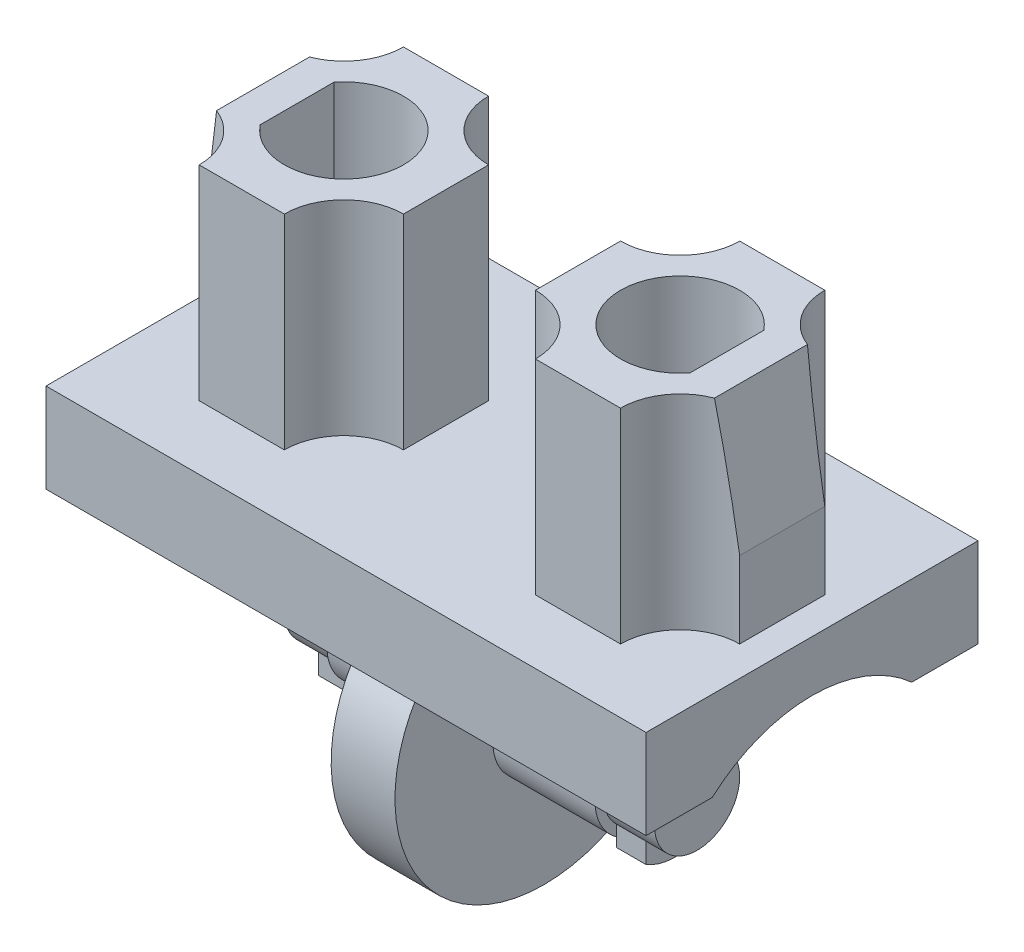
SolidWorks part; units mm, degrees
ref_plane "Front Plane" through (0, 0, 0) normal (0, 0, 1) x (1, 0, 0)
ref_plane "Top Plane" through (0, 0, 0) normal (0, 1, 0) x (1, 0, 0)
ref_plane "Right Plane" through (0, 0, 0) normal (1, 0, 0) x (0, 0, -1)
sketch "Sketch1" plane through (0, 0, 0) normal (1, 0, 0) x (0, 0, -1)
  line L0 (0, 0) -> (0, -4.7) construction
  line L1 (2.3431, -2.1) -> (3.9, -2.1)
  line L2 (-3.9, -2.1) -> (-2.3431, -2.1)
  line L3 (-3.9, -2.1) -> (-3.9, 0)
  line L4 (-3.9, 0) -> (3.9, 0)
  line L5 (3.9, -2.1) -> (3.9, 0)
  line L6 (-3.9, -2.1) -> (3.9, 0) construction
  line L7 (-3.9, 0) -> (3.9, -2.1) construction
  circle A0 centre (0, -4.7) radius 3.5
  point P4 (0, -1.05)
  dimension "D2" = 7
  dimension "D1" = 4.7
  dimension "D3" = 7.8
  dimension "D4" = 2.1
extrude "Hib Base" add sketch "Sketch1" along normal mid plane 14.1 contours A0 L1 L5 L4 L3 L2 region at (0, -0.9029, 0)
extrude "Leg Joint" add sketch "Sketch1<3>" along normal mid plane 1.5 contours A0 region at (0, -4.7, 0)
sketch "Sketch1<3>" plane through (0, 0, 0) normal (1, 0, 0) x (0, 0, -1) same geometry as "Sketch1"
sketch "Sketch2" plane through (0.75, 0, 0) normal (1, 0, 0) x (0, 0, -1)
  circle A0 centre (0, -4.7) radius 1.2
  dimension "D1" = 2.4
extrude "Leg Peg" add sketch "Sketch2" along normal blind 2.4
sketch "Sketch3" plane through (3.15, 0, 0) normal (1, 0, 0) x (0, 0, -1)
  line L0 (-0.6614, -3.95) -> (0.6614, -3.95)
  arc A0 (-0.6614, -3.95) -> (0.6614, -3.95) centre (0, -4.7) ccw
  dimension "D1" = 2
  dimension "D2" = 0.75
extrude "Leg Peg Inner" add sketch "Sketch3" along normal blind 1.2
sketch "Sketch4" plane through (3.15, 0, 0) normal (1, 0, 0) x (0, 0, -1)
  line L2 (-0.7, -5.8893) -> (-0.7, -5.4141)
  line L4 (0.7, -5.8893) -> (0.7, -5.4141)
  arc A0 (-0.6614, -3.95) -> (0.6614, -3.95) centre (0, -4.7) ccw construction
  arc A1 (-0.7, -5.4141) -> (0.7, -5.4141) centre (0, -4.7) ccw
  arc A2 (-0.7, -5.8893) -> (0.7, -5.8893) centre (0, -4.7) ccw
  arc A3 (-0.9128, -3.665) -> (0.9128, -3.665) centre (0, -4.7) ccw construction
  arc A4 (-0.6614, -3.95) -> (0.6614, -3.95) centre (0, -4.7) ccw construction
  point P6 (0, -5.7)
  point P7 (0, 0)
  point P11 (0, -5.7)
  dimension "D2" = 1.4
  dimension "D1" = 0.38
extrude "Leg Lock" add sketch "Sketch4" along normal blind 0.7
sketch "Sketch5" plane through (0, 0, 0) normal (0, 1, 0) x (1, 0, 0)
  line L0 (0, 0) -> (7.05, 0) construction
  line L1 (7.05, -3.9) -> (7.05, 3.9) construction
  line L3 (1.55, -2.4) -> (6.35, -2.4)
  line L4 (1.55, -2.4) -> (1.55, 2.4)
  line L5 (1.55, 2.4) -> (6.35, 2.4)
  line L6 (6.35, -2.4) -> (6.35, 2.4)
  line L7 (1.55, -2.4) -> (6.35, 2.4) construction
  line L8 (1.55, 2.4) -> (6.35, -2.4) construction
  circle A0 centre (1.55, 2.4) radius 1.4
  circle A1 centre (6.35, 2.4) radius 1.4
  circle A2 centre (6.35, -2.4) radius 1.4
  circle A3 centre (1.55, -2.4) radius 1.4
  point P5 (3.95, 0)
  point P11 (0, 0)
  dimension "D4" = 2.8
  dimension "D1" = 1.55
  dimension "D2" = 4.8
  dimension "D3" = 4.8
  dimension "D5" = 4
extrude "Hip Peg" add sketch "Sketch5" along normal blind 4.8 contours A3 L3 A2 L6 A1 L5 A0 L4 region at (3.95, 0, 0)
sketch "Sketch6" plane through (0, 4.8, 0) normal (0, 1, 0) x (1, 0, 0)
  line L0 (4.95, 2.4) -> (2.95, -2.4) construction
  line L1 (5.05, 0.866) -> (5.05, -0.866)
  line L2 (6.35, -1) -> (6.35, 1) construction
  arc A0 (5.05, 0.866) -> (5.05, -0.866) centre (3.95, 0) ccw
  dimension "D1" = 2.8
  dimension "D2" = 1.3
extrude "Hip Cavity" cut sketch "Sketch6" against normal up to surface (4.8 mm away) up to face at (3.95, 0, 0)
sketch "Sketch7" plane through (0, 0, 0) normal (0, 0, 1) x (1, 0, 0)
  line L0 (6.35, 4.8) -> (6.35, 1.8)
  line L1 (6.35, 4.8) -> (6.35, 0) construction
  line L2 (6.35, 1.8) -> (5.85, 4.8)
  line L3 (6.35, 4.8) -> (4.95, 4.8) construction
  line L4 (5.85, 4.8) -> (6.35, 4.8)
  dimension "D1" = 0.5
  dimension "D2" = 3
extrude "Hip Peg Chamfer" cut sketch "Sketch7" against normal through all both and the other way through all
mirror "Mirror1" about plane through (0, 0, 0) normal (1, 0, 0) of "Hip Peg Chamfer", "Hip Cavity", "Hip Peg", "Leg Lock", "Leg Peg Inner", "Leg Peg"
